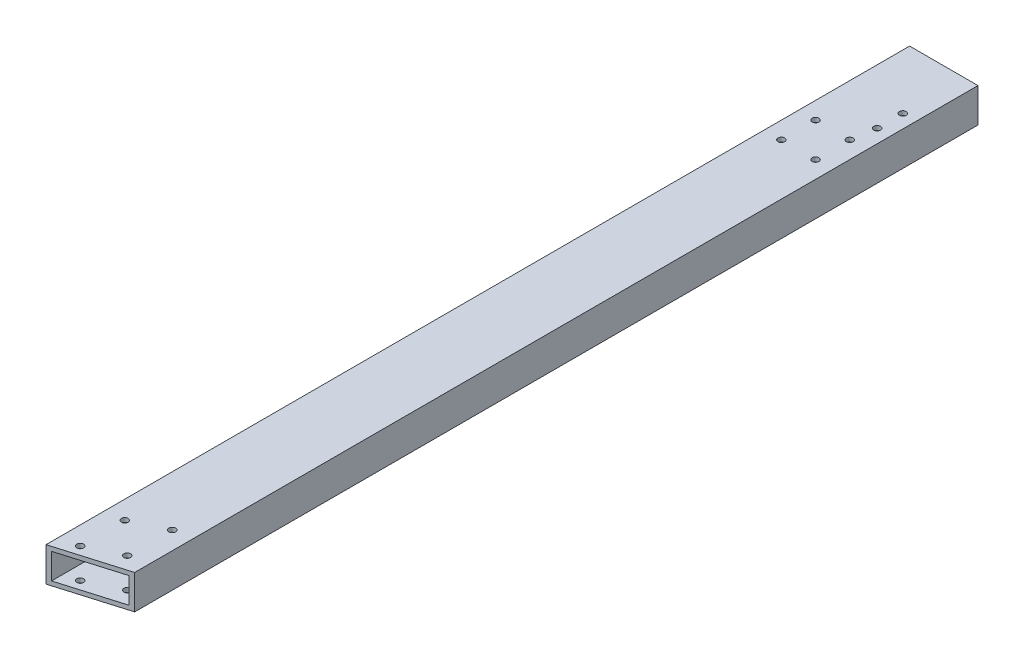
SolidWorks part; units mm, degrees
material "1060 Alloy"
ref_plane "Front Plane" through (0, 0, 0) normal (0, 0, 1) x (1, 0, 0)
ref_plane "Top Plane" through (0, 0, 0) normal (0, 1, 0) x (1, 0, 0)
ref_plane "Right Plane" through (0, 0, 0) normal (1, 0, 0) x (0, 0, -1)
sketch "Sketch1" plane through (0, 0, 0) normal (0, 0, 1) x (1, 0, 0)
  line L0 (-22.225, 9.525) -> (22.225, 9.525)
  line L2 (-25.4, 12.7) -> (25.4, 12.7)
  line L3 (-25.4, 12.7) -> (-25.4, -12.7)
  line L4 (-25.4, -12.7) -> (25.4, -12.7)
  line L5 (25.4, 12.7) -> (25.4, -12.7)
  line L10 (22.225, 9.525) -> (22.225, -9.525)
  line L11 (-22.225, -9.525) -> (22.225, -9.525)
  line L12 (-22.225, 9.525) -> (-22.225, -9.525)
  point P12 (0, 12.7)
  point P14 (25.4, 0)
  dimension "Wall Thickness" = 3.175
  dimension "Outside Width" = 50.8
  dimension "Outside Height" = 25.4
  dimension "Inside Height" = 19.05
  dimension "Inside Width" = 44.45
sketch "Sketch2" plane through (0, 0, 0) normal (1, 0, 0) x (0, 0, -1)
  line L0 (320.675, 0) -> (-320.675, 0)
  point P4 (0, 0)
  point P7 (-320.675, 0)
  point P10 (320.675, 0)
  dimension "Length" = 641.35
sketch "Sketch3" plane through (0, 0, 0) normal (0, 0, 1) x (1, 0, 0)
  line L21 (25.4, 12.7) -> (-25.4, 12.7)
  line L22 (25.4, -12.7) -> (25.4, 12.7)
  line L23 (-25.4, -12.7) -> (25.4, -12.7)
  line L24 (-25.4, 12.7) -> (-25.4, -12.7)
  line L25 (25.4, 12.7) -> (-25.4, 12.7)
  line L26 (25.4, -12.7) -> (25.4, 12.7)
  line L27 (-25.4, -12.7) -> (25.4, -12.7)
  line L28 (-25.4, 12.7) -> (-25.4, -12.7)
  line L29 (22.225, 9.525) -> (-22.225, 9.525)
  line L30 (22.225, -9.525) -> (22.225, 9.525)
  line L31 (-22.225, -9.525) -> (22.225, -9.525)
  line L32 (-22.225, 9.525) -> (-22.225, -9.525)
  line L33 (22.225, 9.525) -> (-22.225, 9.525)
  line L34 (22.225, -9.525) -> (22.225, 9.525)
  line L35 (-22.225, -9.525) -> (22.225, -9.525)
  line L36 (-22.225, 9.525) -> (-22.225, -9.525)
  dimension "D1" = 0
  dimension "D2" = 0
extrude "Boss-Extrude1" add sketch "Sketch3" along normal up to vertex (320.675 mm away) and the other way up to vertex (320.675 mm away) up to point (0, 0, 320.675) other way up to point (0, 0, -320.675)
sketch "Drawing Reference" plane through (0, 0, 0) normal (1, 0, 0) x (0, 0, -1)
  line L0 (-320.675, 0) -> (320.675, 0) construction
  line L1 (0, -12.7) -> (0, 12.7) construction
  line L2 (-320.675, -12.7) -> (320.675, -12.7) construction
  line L5 (-320.675, 12.7) -> (320.675, 12.7) construction
  point P7 (-284.099, 0)
  point P8 (284.099, 0)
  dimension "D1" = 36.576
sketch "Sketch4" plane through (0, 12.7, 0) normal (0, 1, 0) x (1, 0, 0)
  line L0 (-25.4, -320.675) -> (25.4, -305.6274)
  line L1 (25.4, -320.675) -> (25.4, 320.675) construction
  line L2 (25.4, -320.675) -> (-25.4, -320.675)
  dimension "D1" = 16.5
extrude "Cut-Extrude1" cut sketch "Sketch4" against normal through all and the other way through all flip side to cut
sketch "Sketch6" plane through (0, -12.7, 0) normal (0, -1, 0) x (1, 0, 0)
  line L0 (25.4, 305.6274) -> (22.1108, 294.5233) construction
  line L1 (25.4, 279.2824) -> (22.225, 279.2824) construction
  line L2 (25.4, 305.6274) -> (25.4, -320.675) construction
  line L3 (22.225, 279.2824) -> (22.225, 313.1512) construction
  line L4 (22.1108, 294.5233) -> (11.811, 297.5742) construction
  line L5 (-11.811, 250.3501) -> (-11.811, 328.3651) construction
  line L6 (-25.4, 320.675) -> (-27.5213, 313.5136) construction
  line L7 (-25.4, 287.6223) -> (-22.225, 287.6223) construction
  line L8 (-25.4, 320.675) -> (-25.4, -320.675) construction
  line L9 (-22.225, 287.6223) -> (-22.225, 328.3651) construction
  line L10 (-27.5213, 313.5136) -> (-11.811, 308.86) construction
  line L11 (11.811, 250.3501) -> (11.811, 313.1512) construction
  line L12 (-27.5213, 313.5136) -> (-36.5388, 283.071) construction
  line L13 (22.1108, 294.5233) -> (13.0933, 264.0807) construction
  line L14 (-37.6746, 250.3501) -> (48.6057, 250.3501) construction
  line L15 (-11.811, 287.6223) -> (-11.811, 328.3651) construction
  line L16 (11.811, 279.2824) -> (11.811, 313.1512) construction
  line L17 (-36.5388, 283.071) -> (-11.811, 275.7463) construction
  line L18 (13.0933, 264.0807) -> (11.811, 264.4606) construction
  line L19 (-11.811, 308.86) -> (11.811, 264.4606) construction
  line L20 (11.811, 297.5742) -> (-11.811, 275.7463) construction
  point P10 (0, 286.6603)
  dimension "D1" = 10.414
  dimension "D2" = 10.414
hole_wizard "#10 Clearance Hole1" positions "Sketch9" profile "Sketch10" hole size "#10" standard "ANSI Inch"
sketch "Sketch9" plane through (0, 12.7, 0) normal (0, 1, 0) x (1, 0, 0)
  line L0 (13.0933, -264.0807) -> (11.811, -264.4606) construction
  point P0 (-11.811, -275.7463)
  point P3 (-11.811, -308.86)
  point P6 (11.811, -297.5742)
  point P9 (12.0472, -264.3906)
sketch "Sketch10" plane through (-11.811, 12.7, 275.7463) normal (1, 0, 0) x (0, 0, 1)
  line L0 (0, 0) -> (0, 31.9757)
  line L1 (0, 31.9757) -> (2.4892, 30.48)
  line L2 (2.4892, 30.48) -> (2.4892, 0)
  line L5 (2.4892, 0) -> (0, 0)
  line L10 (0, 31.9757) -> (-2.4892, 30.48) construction
  line L11 (0, -6.35) -> (0, 107.95) construction
  dimension "Hole Dia." = 4.9784
  dimension "Hole Depth" = 30.48
  dimension "Drill Angle" = 118
sketch "Sketch12" plane through (0, -12.7, 0) normal (0, -1, 0) x (1, 0, 0)
  line L0 (12.7, -316.23) -> (10.16, -316.23) construction
  line L1 (-10.16, -316.23) -> (-12.7, -316.23) construction
  line L2 (12.7, -299.72) -> (10.16, -299.72) construction
  line L3 (-10.16, -299.72) -> (-12.7, -299.72) construction
hole_wizard "#10 Clearance Hole3" positions "Sketch15" profile "Sketch16" hole size "#10" standard "ANSI Inch"
sketch "Sketch15" plane through (0, -12.7, 0) normal (0, -1, 0) x (-1, 0, 0)
  point P0 (-12.7, 299.72)
  point P3 (12.7, 299.72)
  point P6 (12.7, 316.23)
  point P9 (-12.7, 316.23)
sketch "Sketch16" plane through (12.7, -12.7, -299.72) normal (1, 0, 0) x (0, 0, -1)
  line L0 (0, 0) -> (0, 6.5757)
  line L1 (0, 6.5757) -> (2.4892, 5.08)
  line L2 (2.4892, 5.08) -> (2.4892, 0)
  line L5 (2.4892, 0) -> (0, 0)
  line L10 (0, 6.5757) -> (-2.4892, 5.08) construction
  line L11 (0, -6.35) -> (0, 107.95) construction
  dimension "Hole Dia." = 4.9784
  dimension "Hole Depth" = 5.08
  dimension "Drill Angle" = 118
sketch "Sketch17" plane through (0, -12.7, 0) normal (0, -1, 0) x (1, 0, 0)
  line L0 (12.7, -238.125) -> (-12.7, -238.125) construction
  line L1 (-12.7, -238.125) -> (-12.7, -212.725) construction
  line L2 (-12.7, -212.725) -> (12.7, -212.725) construction
  line L3 (12.7, -212.725) -> (12.7, -238.125) construction
hole_wizard "#10 Clearance Hole4" positions "Sketch18" profile "Sketch19" hole size "#10" standard "ANSI Inch" end condition through all
sketch "Sketch18" plane through (0, -12.7, 0) normal (0, -1, 0) x (-1, 0, 0)
  point P0 (-12.7, 238.125)
  point P3 (12.7, 238.125)
  point P6 (12.7, 212.725)
  point P14 (-12.7, 212.725)
  point P18 (-15.4075, 274.8363)
  point P21 (-15.4075, 255.7863)
sketch "Sketch19" plane through (12.7, -12.7, -238.125) normal (1, 0, 0) x (0, 0, -1)
  line L0 (0, 0) -> (0, 25.4)
  line L1 (0, 25.4) -> (2.4892, 25.4)
  line L2 (2.4892, 25.4) -> (2.4892, 0)
  line L5 (2.4892, 0) -> (0, 0)
  line L11 (0, -6.35) -> (0, 107.95) construction
  dimension "Thru Hole Dia." = 4.9784
  dimension "Thru Hole Depth" = 25.4
equation "\"D1@Drawing Reference\"=\"Outside Width@Sketch1\" * 0.72"
